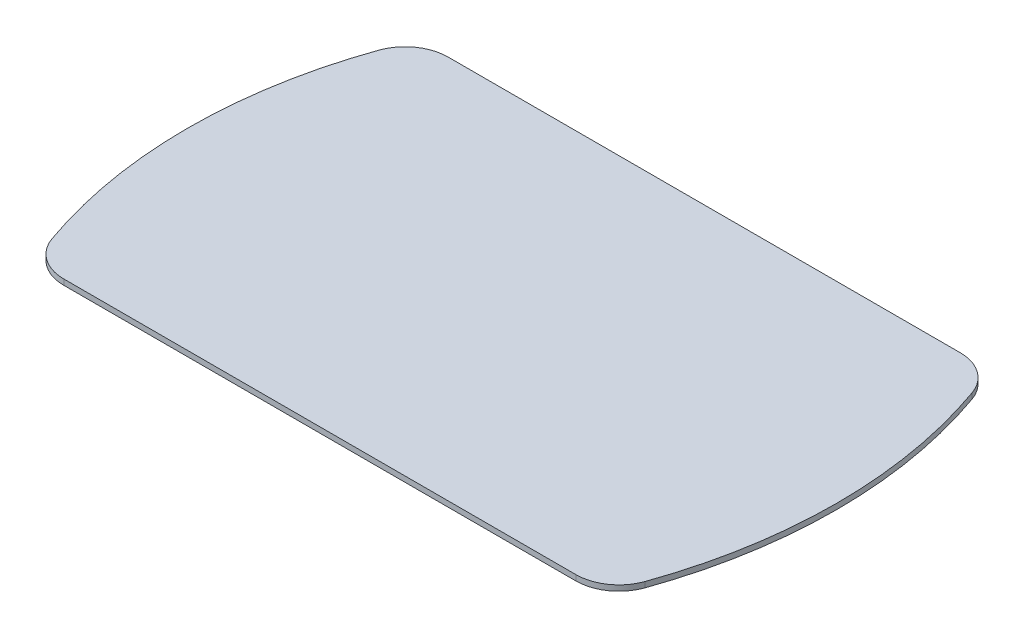
SolidWorks part; units mm, degrees
ref_plane "Front Plane" through (0, 0, 0) normal (0, 0, 1) x (1, 0, 0)
ref_plane "Top Plane" through (0, 0, 0) normal (0, 1, 0) x (1, 0, 0)
ref_plane "Right Plane" through (0, 0, 0) normal (1, 0, 0) x (0, 0, -1)
ref_plane "Plane1" through (0, 0, 0) normal (0, -1, 0) x (1, 0, 0)
sketch "Sketch1" plane through (0, 0, 0) normal (0, -1, 0) x (1, 0, 0)
  line L0 (23.1838, 17.4) -> (-23.1838, 17.4)
  line L1 (-23.1838, -17.4) -> (23.1838, -17.4)
  arc A0 (26.8607, -14.8) -> (26.8607, 14.8) centre (-15, 0) ccw
  arc A1 (26.8607, 14.8) -> (23.1838, 17.4) centre (23.1838, 13.5) ccw
  arc A2 (-23.1838, 17.4) -> (-26.8607, 14.8) centre (-23.1838, 13.5) ccw
  arc A3 (-26.8607, 14.8) -> (-26.8607, -14.8) centre (15, 0) ccw
  arc A4 (-26.8607, -14.8) -> (-23.1838, -17.4) centre (-23.1838, -13.5) ccw
  arc A5 (23.1838, -17.4) -> (26.8607, -14.8) centre (23.1838, -13.5) ccw
extrude "Boss-Extrude1" add sketch "Sketch1" against normal blind 0.5
